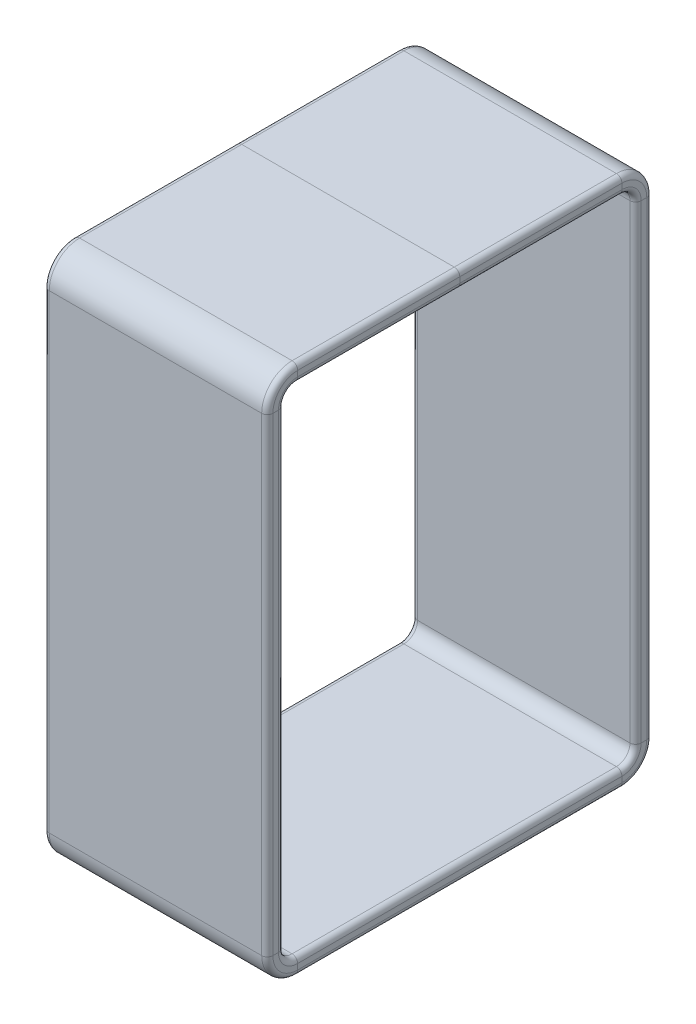
SolidWorks part; units mm, degrees
ref_plane "Front Plane" through (0, 0, 0) normal (0, 0, 1) x (1, 0, 0)
ref_plane "Top Plane" through (0, 0, 0) normal (0, 1, 0) x (1, 0, 0)
ref_plane "Right Plane" through (0, 0, 0) normal (1, 0, 0) x (0, 0, -1)
sketch "Sketch1" plane through (0, 0, 0) normal (1, 0, 0) x (0, 0, -1)
  line L1 (14.5, 23) -> (-14.5, 23)
  line L2 (16.5, 21) -> (16.5, -21)
  line L3 (14.5, -23) -> (-14.5, -23)
  line L4 (-16.5, 21) -> (-16.5, -21)
  line L5 (16.5, 23) -> (-16.5, -23) construction
  line L6 (16.5, -23) -> (-16.5, 23) construction
  arc A0 (-14.5, -23) -> (-16.5, -21) centre (-14.5, -21) cw
  arc A1 (16.5, -21) -> (14.5, -23) centre (14.5, -21) cw
  arc A2 (14.5, 23) -> (16.5, 21) centre (14.5, 21) cw
  arc A3 (-14.5, 23) -> (-16.5, 21) centre (-14.5, 21) ccw
  point P0 (0, 0)
  dimension "D3" = 2
  dimension "D1" = 46
  dimension "D2" = 33
sketch "Sketch2" plane through (0, 0, 0) normal (0, 0, 1) x (1, 0, 0)
  line L0 (0, -23) -> (0, 23) construction
  line L1 (-9.5, 23.7188) -> (9.5, 23.7188)
  line L2 (-10, 23.2188) -> (-10, 22.7188)
  line L3 (-9.5, 22.2188) -> (9.5, 22.2188)
  line L4 (10, 23.2188) -> (10, 22.7188)
  line L5 (-10, 23.7188) -> (10, 22.2188) construction
  line L6 (-10, 22.2188) -> (10, 23.7188) construction
  line L7 (0, 23) -> (0, -23) construction
  arc A0 (9.5, 22.2188) -> (10, 22.7188) centre (9.5, 22.7188) ccw
  arc A1 (9.5, 23.7188) -> (10, 23.2188) centre (9.5, 23.2188) cw
  arc A2 (-10, 22.7188) -> (-9.5, 22.2188) centre (-9.5, 22.7188) ccw
  arc A3 (-9.5, 23.7188) -> (-10, 23.2188) centre (-9.5, 23.2188) ccw
  point P0 (0, 22.9688)
  point P7 (0, 23)
  point P8 (0, 24.2092)
  point P9 (0, 23)
  point P12 (10, 24.9006)
  point P13 (0, 0)
  point P14 (0, 22.8671)
  point P15 (0, 22.9688)
  dimension "D3" = 0.5
  dimension "D1" = 20
  dimension "D2" = 1.5
sweep "Sweep1" add profiles "Sketch2" path "Sketch1"
